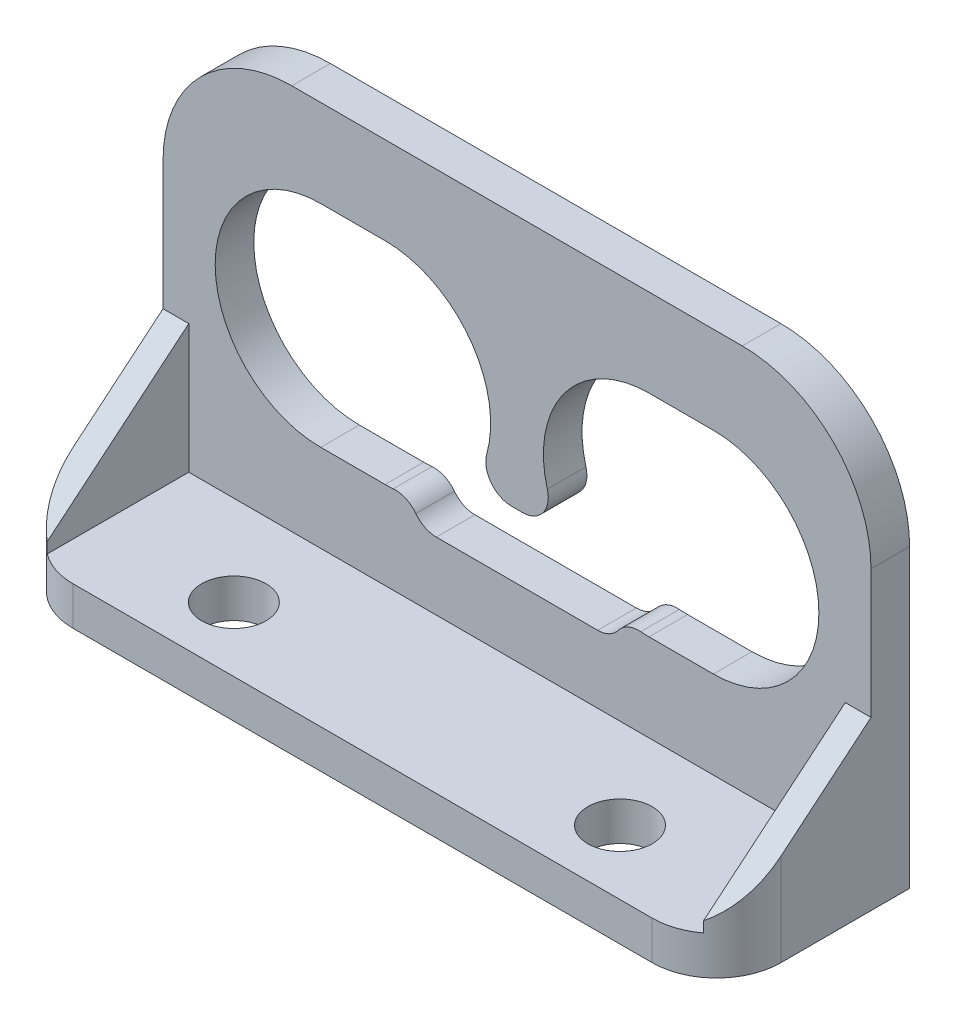
SolidWorks part; units mm, degrees
ref_plane "Front Plane" through (0, 0, 0) normal (0, 0, 1) x (1, 0, 0)
ref_plane "Top Plane" through (0, 0, 0) normal (0, 1, 0) x (1, 0, 0)
ref_plane "Right Plane" through (0, 0, 0) normal (1, 0, 0) x (0, 0, -1)
sketch "Sketch1" plane through (0, 0, 0) normal (0, 1, 0) x (1, 0, 0)
  line L1 (27.5, -7.5) -> (-27.5, -7.5)
  line L2 (27.5, -7.5) -> (27.5, 7.5)
  line L3 (27.5, 7.5) -> (-27.5, 7.5)
  line L4 (-27.5, -7.5) -> (-27.5, 7.5)
  line L5 (27.5, -7.5) -> (-27.5, 7.5) construction
  line L6 (27.5, 7.5) -> (-27.5, -7.5) construction
  point P0 (0, 0)
  dimension "D1" = 15
  dimension "D2" = 55
extrude "Boss-Extrude1" add sketch "Sketch1" along normal blind 3
sketch "Sketch2" plane through (0, 3, 0) normal (0, 1, 0) x (1, 0, 0)
  line L0 (27.5, -7.5) -> (27.5, 7.5) construction
  line L1 (-27.5, 7.5) -> (27.5, 7.5)
  line L2 (-27.5, 7.5) -> (-27.5, 4.5)
  line L3 (-27.5, 4.5) -> (27.5, 4.5)
  line L4 (27.5, 7.5) -> (27.5, 4.5)
  dimension "D1" = 3
extrude "Boss-Extrude2" add sketch "Sketch2" along normal blind 30
sketch "Sketch3" plane through (0, 0, -4.5) normal (0, 0, 1) x (1, 0, 0)
  line L0 (-15.25, 18) -> (-10.25, 18) construction
  line L1 (-15.25, 26.2) -> (-10.25, 26.2)
  line L2 (-15.25, 9.8) -> (-10.25, 9.8)
  line L3 (-27.5, 3) -> (27.5, 3) construction
  line L4 (0, -55) -> (0, 55) construction
  line L5 (15.25, 18) -> (10.25, 18) construction
  line L6 (15.25, 26.2) -> (10.25, 26.2)
  line L7 (15.25, 9.8) -> (10.25, 9.8)
  arc A0 (-15.25, 26.2) -> (-15.25, 9.8) centre (-15.25, 18) ccw
  arc A1 (-10.25, 9.8) -> (-10.25, 26.2) centre (-10.25, 18) ccw
  arc A2 (15.25, 26.2) -> (15.25, 9.8) centre (15.25, 18) cw
  arc A3 (10.25, 9.8) -> (10.25, 26.2) centre (10.25, 18) cw
  point P2 (-12.75, 18)
  point P14 (12.75, 18)
  dimension "D1" = 8.2
  dimension "D2" = 5
  dimension "D3" = 12.75
  dimension "D4" = 15
extrude "Cut-Extrude1" cut sketch "Sketch3" against normal blind 30
sketch "Sketch4" plane through (0, 3, 0) normal (0, 1, 0) x (1, 0, 0)
  line L0 (0, -8.25) -> (0, 8.25) construction
  line L1 (-27.5, -7.5) -> (27.5, -7.5) construction
  circle A0 centre (-15, -2.5) radius 2.5
  circle A1 centre (15, -2.5) radius 2.5
  dimension "D1" = 15
  dimension "D2" = 5
extrude "Cut-Extrude2" cut sketch "Sketch4" against normal blind 30
sketch "Sketch5" plane through (-27.5, 0, 0) normal (-1, 0, 0) x (0, 0, 1)
  line L0 (7.5, 3) -> (-4.5, 3)
  line L1 (-4.5, 3) -> (-4.5, 13)
  line L2 (-4.5, 33) -> (-4.5, 3) construction
  line L3 (-4.5, 13) -> (7.5, 3)
extrude "Boss-Extrude3" add sketch "Sketch5" against normal blind 2
mirror "Mirror1" about plane through (0, 0, 0) normal (1, 0, 0) of "Boss-Extrude3"
fillet "Fillet1" radius 10 2 edges at (27.5, 33, -6) (-27.5, 33, -6)
sketch "Sketch6" plane through (0, 0, -7.5) normal (0, 0, -1) x (-1, 0, 0)
  line L0 (-27.5, 0) -> (27.5, 0) construction
  line L1 (7.5, 8.25) -> (-7.5, 8.25)
  line L2 (7.5, 8.25) -> (7.5, 13.25)
  line L3 (7.5, 13.25) -> (-7.5, 13.25)
  line L4 (-7.5, 8.25) -> (-7.5, 13.25)
  point P4 (0, 8.25)
  dimension "D1" = 0
  dimension "D2" = 15
  dimension "D3" = 5
  dimension "D4" = 8.25
extrude "Cut-Extrude3" cut sketch "Sketch6" against normal blind 10
fillet "Fillet2" radius 2 2 edges at (-7.5, 10.2749, -6) (7.5, 10.2749, -6)
fillet "Fillet3" radius 2 2 edges at (3.5659, 13.25, -6) (-3.5659, 13.25, -6)
fillet "Fillet4" radius 2 2 edges at (-7.5, 8.25, -6) (7.5, 8.25, -6)
fillet "Fillet5" radius 5 2 edges at (27.5, 1.5, 7.5) (-27.5, 1.5, 7.5)
